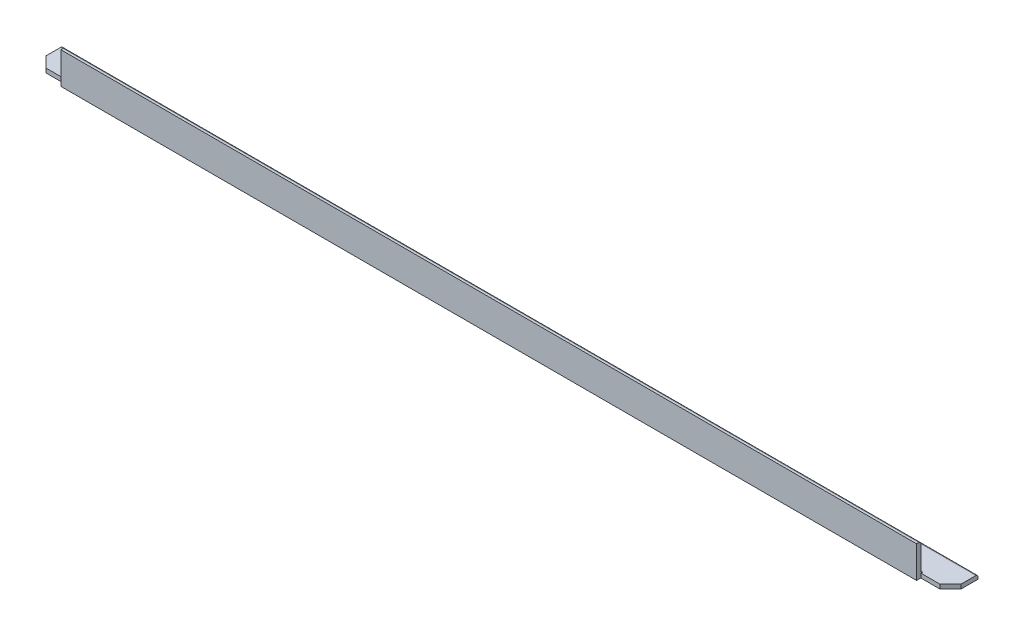
SolidWorks part; units mm, degrees
material "1060 Сплав"
ref_plane "Front" through (0, 0, 0) normal (0, 0, 1) x (1, 0, 0)
ref_plane "Top" through (0, 0, 0) normal (0, 1, 0) x (1, 0, 0)
ref_plane "Right" through (0, 0, 0) normal (1, 0, 0) x (0, 0, -1)
sketch "Эскиз1" plane through (0, 0, 0) normal (1, 0, 0) x (0, 0, -1)
  line L0 (0, 0) -> (0, 15)
  line L1 (0, 0) -> (15, 0)
  line L2 (0, 15) -> (1, 15)
  line L3 (2, 14) -> (2, 3)
  line L4 (3, 2) -> (14, 2)
  line L5 (15, 1) -> (15, 0)
  arc A0 (14, 2) -> (15, 1) centre (14, 1) cw
  arc A1 (1, 15) -> (2, 14) centre (1, 14) cw
  arc A2 (2, 3) -> (3, 2) centre (3, 3) ccw
  point P9 (15, 2)
  point P12 (2, 15)
  dimension "D5" = 1
  dimension "D1" = 15
  dimension "D2" = 15
  dimension "D3" = 2
  dimension "D4" = 2
extrude "Бобышка-Вытянуть1" add sketch "Эскиз1" along normal blind 432
sketch "Эскиз6" plane through (432, 0, 0) normal (1, 0, 0) x (0, 0, -1)
  line L0 (0, 0) -> (15, 0) construction
  line L1 (0, 15) -> (2, 15)
  line L2 (0, 15) -> (0, 0)
  line L3 (0, 0) -> (2, 0)
  line L4 (2, 0) -> (2, 2)
  line L5 (2, 2) -> (3, 2)
  line L6 (3, 2) -> (3, 15)
  line L7 (3, 15) -> (2, 15)
extrude "Вырез-Вытянуть5" cut sketch "Эскиз6" against normal blind 14
sketch "Эскиз7" plane through (0, 0, 0) normal (-1, 0, 0) x (0, 0, 1)
  line L0 (0, 0) -> (-15, 0) construction
  line L1 (0, 15) -> (-2, 15)
  line L2 (0, 15) -> (0, 0)
  line L3 (0, 0) -> (-2, 0)
  line L4 (-3, 2) -> (-2, 2)
  line L5 (-2, 2) -> (-2, 0)
  line L6 (-3, 2) -> (-3, 15)
  line L7 (-3, 15) -> (-2, 15)
extrude "Вырез-Вытянуть6" cut sketch "Эскиз7" against normal blind 14
sketch "Эскиз9" plane through (0, 2, 0) normal (0, 1, 0) x (1, 0, 0)
  line L0 (0, 2) -> (0, 7)
  line L1 (0, 14) -> (0, 2) construction
  line L2 (0, 7) -> (5, 2)
  line L3 (14, 2) -> (0, 2) construction
  line L4 (5, 2) -> (0, 2)
  line L5 (432, 2) -> (432, 7)
  line L6 (432, 14) -> (432, 2) construction
  line L7 (432, 7) -> (427, 2)
  line L8 (418, 2) -> (432, 2) construction
  line L9 (427, 2) -> (432, 2)
  dimension "D1" = 5
  dimension "D2" = 5
  dimension "D3" = 5
  dimension "D4" = 5
extrude "Вырез-Вытянуть7" cut sketch "Эскиз9" against normal through all
sketch "Эскиз10" plane through (0, 2, 0) normal (0, 1, 0) x (1, 0, 0)
  line L0 (432, 15) -> (0, 15) construction
  line L1 (0, 14) -> (0, 7) construction
  line L2 (432, 14) -> (432, 7) construction
  circle A0 centre (40, 8) radius 2.3
  circle A1 centre (392, 8) radius 2.3
  dimension "D1" = 4.6
  dimension "D2" = 7
  dimension "D3" = 40
  dimension "D4" = 4.6
  dimension "D5" = 7
  dimension "D6" = 40
extrude "Вырез-Вытянуть8" cut sketch "Эскиз10" against normal through all
chamfer "Фаска1" distance 2.05 angle 45 2 edges at (40, 2, -5.7) (392, 2, -5.7)
